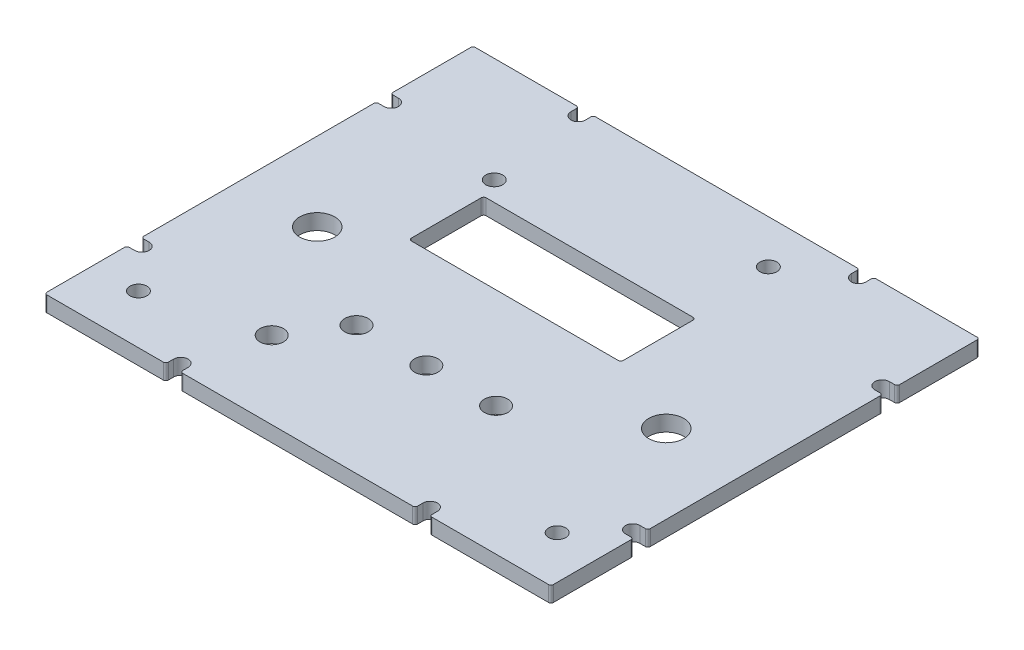
SolidWorks part; units mm, degrees
ref_plane "Front Plane" through (0, 0, 0) normal (0, 0, 1) x (1, 0, 0)
ref_plane "Top Plane" through (0, 0, 0) normal (0, 1, 0) x (1, 0, 0)
ref_plane "Right Plane" through (0, 0, 0) normal (1, 0, 0) x (0, 0, -1)
sketch "Sketch1" plane through (0, 0, 0) normal (0, 1, 0) x (1, 0, 0)
  line L1 (-51.5938, -43.6562) -> (51.5937, -43.6562)
  line L2 (-51.5938, -43.6562) -> (-51.5938, 43.6562)
  line L3 (-51.5938, 43.6562) -> (51.5937, 43.6562)
  line L4 (51.5937, -43.6562) -> (51.5937, 43.6562)
  line L5 (-51.5938, -43.6562) -> (51.5937, 43.6562) construction
  line L6 (-51.5938, 43.6562) -> (51.5937, -43.6562) construction
  point P0 (0, 0)
  dimension "D1" = 103.1875
  dimension "D2" = 87.3125
extrude "Boss-Extrude1" add sketch "Sketch1" along normal blind 3.175
hole_wizard "#29 (0.136) Diameter Hole1" positions "Sketch2" profile "Sketch3" hole size "#29" standard "ANSI Inch" end condition through all
sketch "Sketch2" plane through (0, 3.175, 0) normal (0, 1, 0) x (1, 0, 0)
  point P0 (-25.8318, 22.2123)
  point P3 (17.4498, 34.7853)
  point P6 (42.8498, -33.6423)
  point P9 (-42.4688, -33.6423)
sketch "Sketch3" plane through (-25.8318, 3.175, -22.2123) normal (1, 0, 0) x (0, 0, 1)
  line L0 (0, 0) -> (0, 3.175)
  line L1 (0, 3.175) -> (1.7272, 3.175)
  line L2 (1.7272, 3.175) -> (1.7272, 0)
  line L5 (1.7272, 0) -> (0, 0)
  line L11 (0, -6.35) -> (0, 107.95) construction
  dimension "Thru Hole Dia." = 3.4544
  dimension "Thru Hole Depth" = 3.175
hole_wizard "9/32 (0.28125) Diameter Hole1" positions "Sketch4" profile "Sketch5" hole size "9/32" standard "ANSI Inch" end condition through all
sketch "Sketch4" plane through (0, 3.175, 0) normal (0, 1, 0) x (1, 0, 0)
  point P0 (-35.56, -4.1275)
  point P3 (35.56, -4.1275)
sketch "Sketch5" plane through (-35.56, 3.175, 4.1275) normal (1, 0, 0) x (0, 0, 1)
  line L0 (0, 0) -> (0, 3.175)
  line L1 (0, 3.175) -> (3.5719, 3.175)
  line L2 (3.5719, 3.175) -> (3.5719, 0)
  line L5 (3.5719, 0) -> (0, 0)
  line L11 (0, -6.35) -> (0, 107.95) construction
  dimension "Thru Hole Dia." = 7.1437
  dimension "Thru Hole Depth" = 3.175
hole_wizard "3/16 (0.1875) Diameter Hole1" positions "Sketch6" profile "Sketch7" hole size "3/16" standard "ANSI Inch" end condition through all
sketch "Sketch6" plane through (0, 3.175, 0) normal (0, 1, 0) x (1, 0, 0)
  point P13 (-14.224, -17.4625)
  point P15 (0, -17.4625)
  point P17 (14.224, -17.4625)
  point P19 (-21.082, -27.8765)
sketch "Sketch7" plane through (-14.224, 3.175, 17.4625) normal (1, 0, 0) x (0, 0, 1)
  line L0 (0, 0) -> (0, 3.175)
  line L1 (0, 3.175) -> (2.3812, 3.175)
  line L2 (2.3812, 3.175) -> (2.3812, 0)
  line L5 (2.3812, 0) -> (0, 0)
  line L11 (0, -6.35) -> (0, 107.95) construction
  dimension "Thru Hole Dia." = 4.7625
  dimension "Thru Hole Depth" = 3.175
sketch "Sketch8" plane through (0, 3.175, 0) normal (0, 1, 0) x (1, 0, 0)
  line L0 (-24.003, 18.2245) -> (19.177, 18.2245)
  line L5 (19.177, 18.2245) -> (19.177, 2.9845)
  line L6 (-24.003, 2.9845) -> (19.177, 2.9845)
  line L7 (-24.003, 18.2245) -> (-24.003, 2.9845)
  circle A0 centre (-25.8318, 22.2123) radius 1.7272 construction
  dimension "D1" = 1.8288
  dimension "D2" = 45.0088
  dimension "D3" = 3.9878
  dimension "D4" = 19.2278
extrude "Cut-Extrude1" cut sketch "Sketch8" against normal through all
sketch "Sketch9" plane through (0, 3.175, 0) normal (0, 1, 0) x (1, 0, 0)
  line L0 (-51.5938, 43.6562) -> (51.5937, -43.6562) construction
  line L1 (51.5937, 43.6562) -> (-51.5938, 43.6562) construction
  line L2 (50.0062, -42.0687) -> (-50.0063, -42.0687) construction
  line L3 (50.0062, -42.0687) -> (50.0062, 42.0687) construction
  line L4 (50.0062, 42.0687) -> (-50.0063, 42.0687) construction
  line L5 (-50.0063, -42.0687) -> (-50.0063, 42.0687) construction
  line L6 (50.0062, -42.0687) -> (-50.0063, 42.0687) construction
  line L7 (50.0062, 42.0687) -> (-50.0063, -42.0687) construction
  line L8 (-51.5938, 43.6562) -> (-51.5938, -43.6562) construction
  line L9 (-50.0063, 26.8732) -> (-51.5938, 26.8732)
  line L10 (-50.0063, 23.9268) -> (-51.5938, 23.9268)
  line L11 (-51.5938, 26.8732) -> (-51.5938, 23.9268)
  line L12 (-50.0063, -23.9268) -> (-51.5938, -23.9268)
  line L13 (-51.5938, -23.9268) -> (-51.5938, -26.8732)
  line L14 (-50.0063, -26.8732) -> (-51.5938, -26.8732)
  line L15 (0, 0) -> (0, 12.7264) construction
  line L16 (50.0063, -26.8732) -> (51.5938, -26.8732)
  line L17 (51.5938, -23.9268) -> (51.5938, -26.8732)
  line L18 (50.0063, -23.9268) -> (51.5938, -23.9268)
  line L19 (51.5938, 26.8732) -> (51.5938, 23.9268)
  line L20 (50.0063, 23.9268) -> (51.5938, 23.9268)
  line L21 (50.0063, 26.8732) -> (51.5938, 26.8732)
  arc A0 (-50.0063, 23.9268) -> (-50.0063, 26.8732) centre (-50.0063, 25.4) ccw
  arc A1 (-50.0063, -26.8732) -> (-50.0063, -23.9268) centre (-50.0063, -25.4) ccw
  arc A2 (50.0063, -26.8732) -> (50.0063, -23.9268) centre (50.0063, -25.4) cw
  arc A3 (50.0063, 23.9268) -> (50.0063, 26.8732) centre (50.0063, 25.4) cw
  point P4 (0, 0)
  point P16 (-50.0063, 0)
  dimension "D3" = 25.4
  dimension "D5" = 1.4732
  dimension "D1" = 1.5875
  dimension "D2" = 1.5875
  dimension "D6" = 25.4
  dimension "D4" = 2
extrude "Cut-Extrude2" cut sketch "Sketch9" against normal through all
fillet "Fillet1" radius 0.508 12 edges at (51.5938, 1.5875, -23.9268) (51.5938, 1.5875, -26.8732) (51.5938, 1.5875, 23.9268) (51.5938, 1.5875, 26.8732) (-51.5938, 1.5875, 23.9268) (-51.5938, 1.5875, 26.8732) (-51.5938, 1.5875, -23.9268) (-51.5938, 1.5875, -26.8732) (-24.003, 1.5875, -2.9845) (19.177, 1.5875, -2.9845) (19.177, 1.5875, -18.2245) (-24.003, 1.5875, -18.2245)
sketch "Sketch10" plane through (0, 3.175, 0) normal (0, 1, 0) x (1, 0, 0)
  line L0 (-51.5938, -43.6562) -> (51.5937, -43.6562) construction
  line L1 (50.0062, 42.0688) -> (-50.0062, 42.0688) construction
  line L2 (50.0062, 42.0688) -> (50.0062, -42.0687) construction
  line L3 (50.0062, -42.0687) -> (26.8732, -42.0687) construction
  line L4 (-50.0062, 42.0688) -> (-50.0062, -42.0687) construction
  line L5 (50.0062, 42.0688) -> (-50.0062, -42.0687) construction
  line L6 (50.0062, -42.0687) -> (-50.0062, 42.0688) construction
  line L7 (51.5937, -23.4188) -> (51.5937, 23.4188) construction
  line L10 (0, 0) -> (0, -43.6562) construction
  line L11 (-26.8732, -42.0687) -> (-50.0062, -42.0687) construction
  line L12 (-27.1018, 42.0687) -> (-27.1018, 43.6562)
  line L13 (26.8732, -42.0687) -> (26.8732, -43.6562)
  line L14 (26.8732, -43.6562) -> (23.9268, -43.6562)
  line L15 (23.9268, -42.0687) -> (23.9268, -43.6562)
  line L16 (23.9268, -42.0687) -> (-23.9268, -42.0687) construction
  line L17 (-23.9268, -42.0687) -> (-23.9268, -43.6562)
  line L18 (-23.9268, -43.6562) -> (-26.8732, -43.6562)
  line L19 (-26.8732, -42.0687) -> (-26.8732, -43.6562)
  line L20 (-27.1018, 43.6562) -> (-30.0482, 43.6562)
  line L21 (-30.0482, 42.0687) -> (-30.0482, 43.6562)
  line L22 (30.0482, 43.6562) -> (27.1018, 43.6562)
  line L23 (30.0482, 42.0687) -> (30.0482, 43.6562)
  line L24 (27.1018, 42.0687) -> (27.1018, 43.6562)
  arc A0 (26.8732, -42.0687) -> (23.9268, -42.0687) centre (25.4, -42.0687) ccw
  arc A1 (-23.9268, -42.0687) -> (-26.8732, -42.0687) centre (-25.4, -42.0687) ccw
  arc A2 (-27.1018, 42.0687) -> (-30.0482, 42.0687) centre (-28.575, 42.0687) cw
  arc A3 (30.0482, 42.0687) -> (27.1018, 42.0687) centre (28.575, 42.0687) cw
  point P0 (0, 0)
  dimension "D3" = 2.9464
  dimension "D4" = 25.4
  dimension "D5" = 25.4
  dimension "D6" = 28.575
  dimension "D7" = 28.575
  dimension "D1" = 1.5875
  dimension "D2" = 1.5875
extrude "Cut-Extrude3" cut sketch "Sketch10" against normal through all
fillet "Fillet2" radius 0.508 12 edges at (30.0482, 1.5875, -43.6562) (27.1018, 1.5875, -43.6562) (-30.0482, 1.5875, -43.6562) (-27.1018, 1.5875, -43.6562) (-23.9268, 1.5875, 43.6562) (-26.8732, 1.5875, 43.6562) (23.9268, 1.5875, 43.6562) (26.8732, 1.5875, 43.6562) (51.5937, 1.5875, 43.6562) (51.5937, 1.5875, -43.6562) (-51.5938, 1.5875, -43.6562) (-51.5938, 1.5875, 43.6562)
